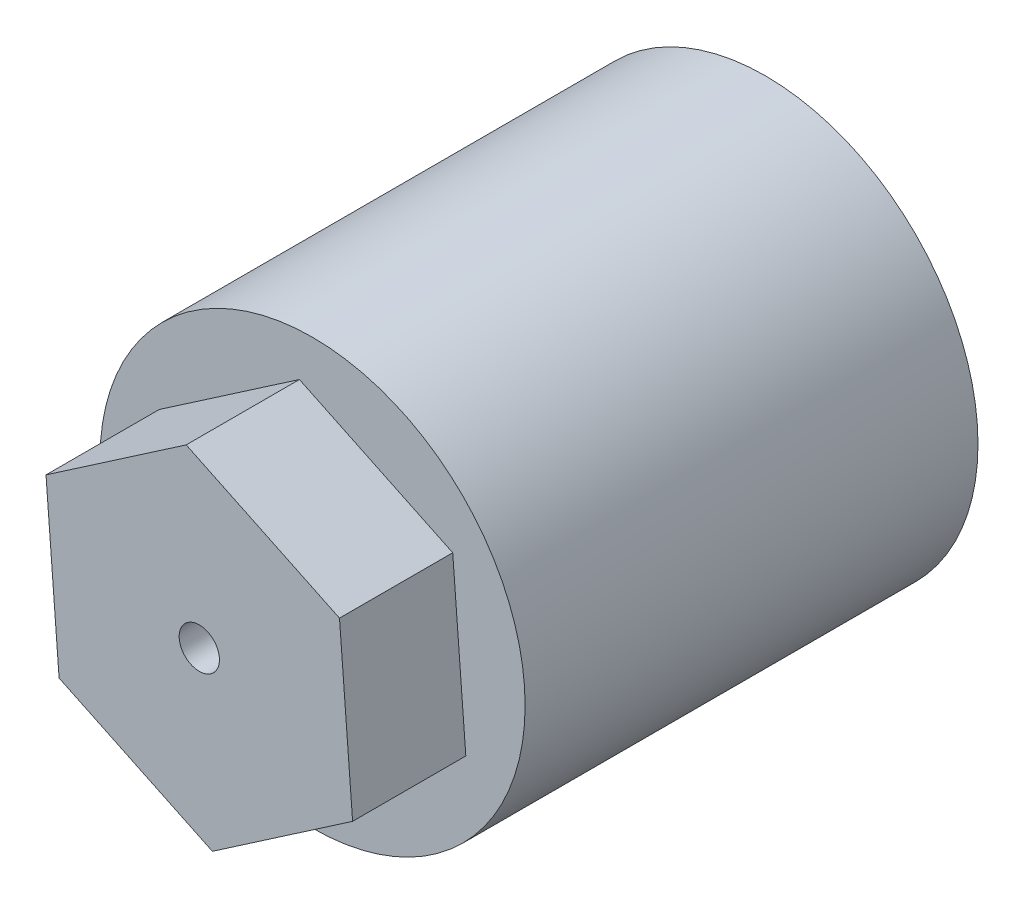
SolidWorks part; units mm, degrees
ref_plane "Front Plane" through (0, 0, 0) normal (0, 0, 1) x (1, 0, 0)
ref_plane "Top Plane" through (0, 0, 0) normal (0, 1, 0) x (1, 0, 0)
ref_plane "Right Plane" through (0, 0, 0) normal (1, 0, 0) x (0, 0, -1)
sketch "Sketch1" plane through (0, 0, 0) normal (0, 0, 1) x (1, 0, 0)
  line L1 (5.5723, 3.8184) -> (-0.5207, 6.7349)
  line L2 (-0.5207, 6.7349) -> (-6.0929, 2.9165)
  line L3 (-6.0929, 2.9165) -> (-5.5723, -3.8184)
  line L4 (-5.5723, -3.8184) -> (0.5207, -6.7349)
  line L5 (0.5207, -6.7349) -> (6.0929, -2.9165)
  line L6 (6.0929, -2.9165) -> (5.5723, 3.8184)
  circle A0 centre (0, 0) radius 5.85 construction
extrude "Boss-Extrude1" add sketch "Sketch1" along normal blind 4.5
sketch "Sketch2" plane through (0, 0, 4.5) normal (0, 0, 1) x (1, 0, 0)
  circle A0 centre (0, 0) radius 0.8
sketch "Sketch4" plane through (0, 0, 0) normal (0, 0, -1) x (-1, 0, 0)
  circle A0 centre (0, 0) radius 8.45
extrude "Boss-Extrude2" add sketch "Sketch4" along normal blind 18
extrude "Boss-Extrude3" add sketch "Sketch1<2>" along normal blind 4.5
sketch "Sketch1<2>" plane through (0, 0, 0) normal (0, 0, 1) x (1, 0, 0) same geometry as "Sketch1"
extrude "Cut-Extrude2" cut sketch "Sketch2" against normal blind 6.5
extrude "Boss-Extrude4" add sketch "Sketch1<3>" along normal blind 4.5
sketch "Sketch1<3>" plane through (0, 0, 0) normal (0, 0, 1) x (1, 0, 0) same geometry as "Sketch1"
extrude "Cut-Extrude4" cut sketch "Sketch2<2>" against normal blind 6
sketch "Sketch2<2>" plane through (0, 0, 4.5) normal (0, 0, 1) x (1, 0, 0) same geometry as "Sketch2"
sketch "Sketch5" plane through (0, 0, -18) normal (0, 0, -1) x (-1, 0, 0)
  line L1 (-1.9659, -1.8507) -> (1.9659, -1.8507)
  line L3 (-1.9659, 1.8507) -> (1.9659, 1.8507)
  arc A0 (-1.9659, 1.8507) -> (-1.9659, -1.8507) centre (0, 0) ccw
  arc A1 (1.9659, -1.8507) -> (1.9659, 1.8507) centre (0, 0) ccw
extrude "Cut-Extrude5" cut sketch "Sketch5" against normal blind 16
